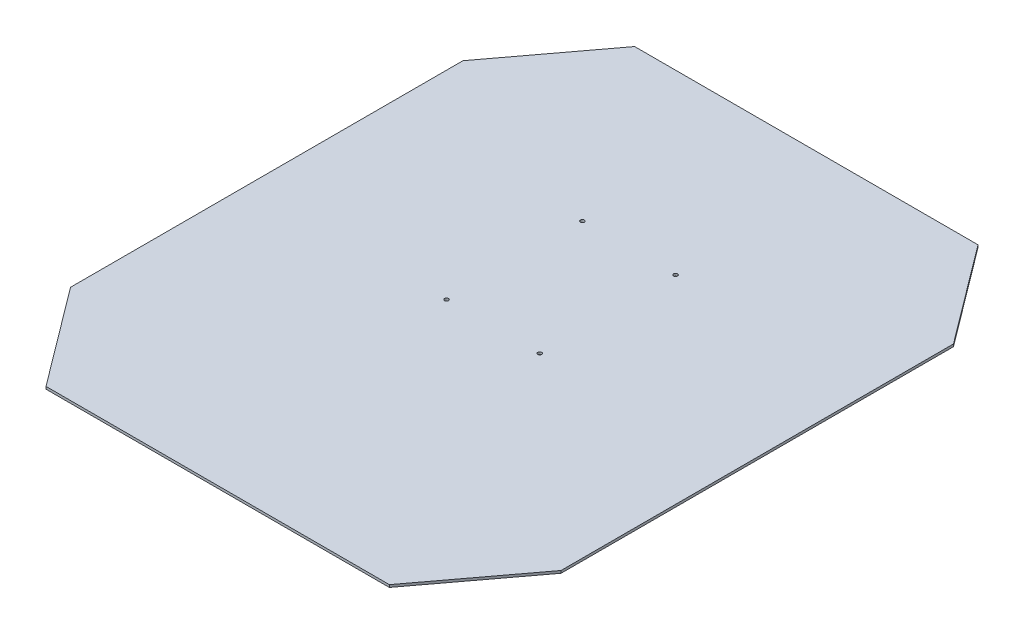
SolidWorks part; units mm, degrees
ref_plane "Front Plane" through (0, 0, 0) normal (0, 0, 1) x (1, 0, 0)
ref_plane "Top Plane" through (0, 0, 0) normal (0, 1, 0) x (1, 0, 0)
ref_plane "Right Plane" through (0, 0, 0) normal (1, 0, 0) x (0, 0, -1)
sketch "Sketch1" plane through (0, 0, 0) normal (0, 1, 0) x (1, 0, 0)
  line L0 (-500, 400) -> (-350, 600)
  line L1 (-500, 600) -> (500, 600)
  line L2 (-500, 600) -> (-500, -600)
  line L3 (-500, -600) -> (500, -600)
  line L4 (500, 600) -> (500, -600)
  line L5 (-500, 600) -> (500, -600) construction
  line L6 (-500, -600) -> (500, 600) construction
  line L7 (0, 600) -> (0, -600) construction
  line L8 (-500, 0) -> (500, 0) construction
  line L9 (500, 400) -> (350, 600)
  line L10 (500, -400) -> (350, -600)
  line L11 (-500, -400) -> (-350, -600)
  point P0 (0, 0)
  dimension "D1" = 1200
  dimension "D2" = 1000
  dimension "D3" = 200
  dimension "D4" = 150
extrude "Boss-Extrude1" add sketch "Sketch1" along normal blind 5 contours L2 L11 L3 L10 L4 L9 L1 L0 region at (0, 0, 0)
sketch "Sketch2" plane through (0, 5, 0) normal (0, 1, 0) x (1, 0, 0)
  line L0 (0, 600) -> (0, -600) construction
  line L1 (-350, 600) -> (350, 600) construction
  line L2 (-350, -600) -> (350, -600) construction
  line L3 (-500, 100) -> (500, 100) construction
  line L4 (-500, 400) -> (-500, -400) construction
  line L5 (500, 400) -> (500, -400) construction
  circle A0 centre (95, 238.5) radius 4
  circle A1 centre (-95, 238.5) radius 4
  circle A2 centre (95, -38.5) radius 4
  circle A3 centre (-95, -38.5) radius 4
  dimension "D2" = 8
  dimension "D1" = 500
  dimension "D3" = 95
  dimension "D4" = 138.5
extrude "Cut-Extrude1" cut sketch "Sketch2" against normal through all
